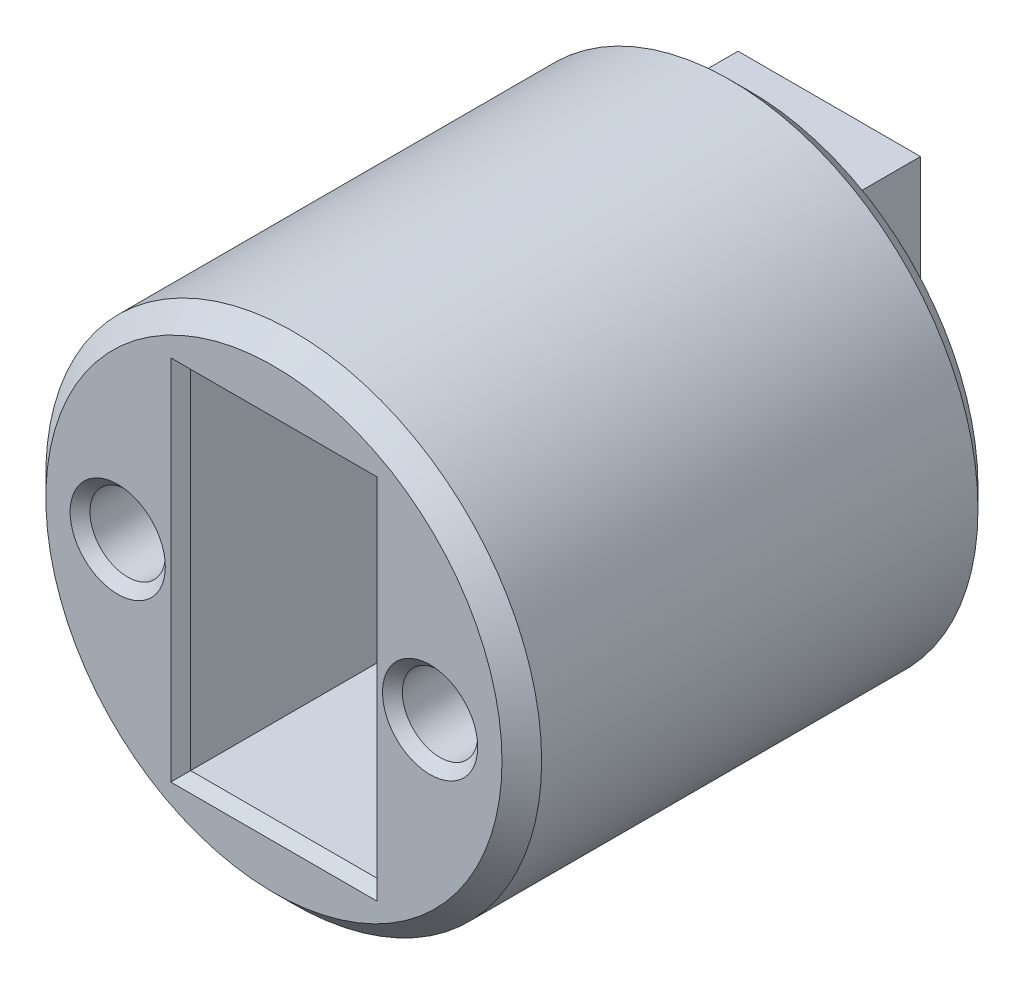
SolidWorks part; units mm, degrees
material "ABS"
ref_plane "Alzado" through (0, 0, 0) normal (0, 0, 1) x (1, 0, 0)
ref_plane "Planta" through (0, 0, 0) normal (0, 1, 0) x (1, 0, 0)
ref_plane "Vista lateral" through (0, 0, 0) normal (1, 0, 0) x (0, 0, -1)
sketch "Croquis1" plane through (0, 0, 0) normal (0, 0, 1) x (1, 0, 0)
  circle A0 centre (0, 0) radius 12.5
  dimension "D1" = 25
extrude "Saliente-Extruir1" add sketch "Croquis1" along normal blind 24
sketch "Croquis2" plane through (0, 0, 24) normal (0, 0, 1) x (1, 0, 0)
  line L1 (-4.7, 8.7625) -> (4.7, 8.7625)
  line L2 (-4.7, 8.7625) -> (-4.7, -8.7625)
  line L3 (-4.7, -8.7625) -> (4.7, -8.7625)
  line L4 (4.7, 8.7625) -> (4.7, -8.7625)
  line L5 (-4.7, 8.7625) -> (4.7, -8.7625) construction
  line L6 (-4.7, -8.7625) -> (4.7, 8.7625) construction
  point P0 (0, 0)
  dimension "D1" = 9.4
  dimension "D2" = 17.525
extrude "Cortar-Extruir1" cut sketch "Croquis2" against normal blind 18
sketch "Croquis3" plane through (0, 0, 0) normal (0, 0, -1) x (-1, 0, 0)
  line L1 (-4.6, 8.95) -> (4.6, 8.95)
  line L2 (-4.6, 8.95) -> (-4.6, -8.95)
  line L3 (-4.6, -8.95) -> (4.6, -8.95)
  line L4 (4.6, 8.95) -> (4.6, -8.95)
  line L5 (-4.6, 8.95) -> (4.6, -8.95) construction
  line L6 (-4.6, -8.95) -> (4.6, 8.95) construction
  point P0 (0, 0)
  dimension "D1" = 9.2
  dimension "D2" = 17.9
extrude "Saliente-Extruir2" add sketch "Croquis3" along normal blind 5
chamfer "Chaflán1" distance 1 angle 45 4 edges at (-4.6, 0, -5) (0, -8.95, -5) (0, 8.95, -5) (4.6, 0, -5)
chamfer "Chaflán2" distance 1 angle 45 1 edges at (12.5, 0, 0)
sketch "Croquis4" plane through (0, 0, 24) normal (0, 0, 1) x (1, 0, 0)
  line L0 (0, 17.1892) -> (0, -16.9535) construction
  circle A0 centre (-7.875, 0) radius 1.9
  circle A1 centre (7.875, 0) radius 1.9
  dimension "D2" = 3.8
  dimension "D1" = 15.75
extrude "Cortar-Extruir2" cut sketch "Croquis4" against normal through all
chamfer "Chaflán3" distance 1 angle 45 1 edges at (12.5, 0, 24)
sketch "Croquis5" plane through (0, 0, 6) normal (0, 0, 1) x (1, 0, 0)
  line L1 (-3, 7) -> (3, 7)
  line L2 (-3, 7) -> (-3, -7)
  line L3 (-3, -7) -> (3, -7)
  line L4 (3, 7) -> (3, -7)
  line L5 (-3, 7) -> (3, -7) construction
  line L6 (-3, -7) -> (3, 7) construction
  point P0 (0, 0)
  dimension "D1" = 14
  dimension "D2" = 6
extrude "Cortar-Extruir3" cut sketch "Croquis5" against normal through all
chamfer "Chaflán4" distance 1.7 angle 45 4 edges at (4.7, 0, 6) (0, 8.7625, 6) (0, -8.7625, 6) (-4.7, 0, 6)
chamfer "Chaflán5" distance 0.5 angle 45 2 edges at (-5.975, 0, 24) (5.975, 0, 24)
chamfer "Chaflán6" distance 0.5 angle 45 4 edges at (0, -8.7625, 24) (4.7, 0, 24) (-4.7, 0, 24) (0, 8.7625, 24)
